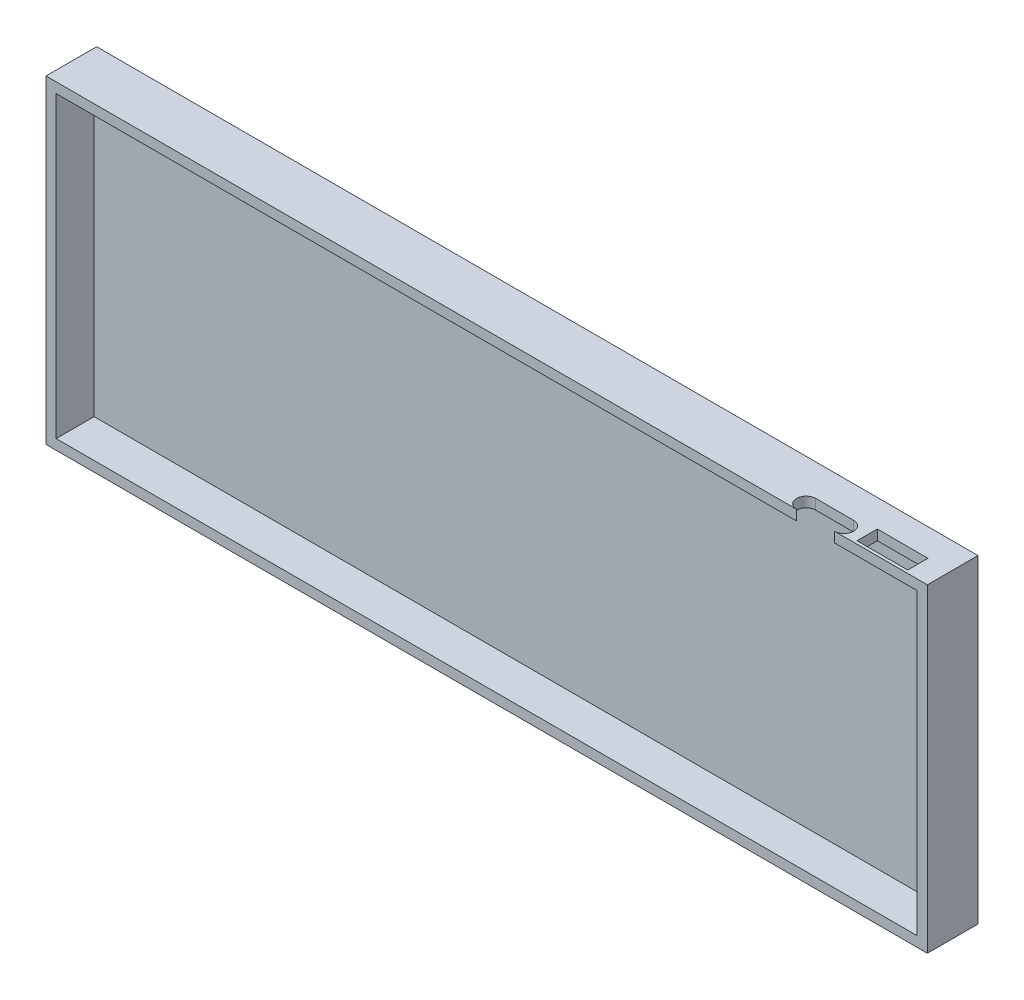
SolidWorks part; units mm, degrees
ref_plane "Front Plane" through (0, 0, 0) normal (0, 0, 1) x (1, 0, 0)
ref_plane "Top Plane" through (0, 0, 0) normal (0, 1, 0) x (1, 0, 0)
ref_plane "Right Plane" through (0, 0, 0) normal (1, 0, 0) x (0, 0, -1)
sketch "Sketch1" plane through (0, 0, 0) normal (0, 0, 1) x (1, 0, 0)
  line L1 (174, 63) -> (-174, 63)
  line L2 (174, 63) -> (174, -63)
  line L3 (174, -63) -> (-174, -63)
  line L4 (-174, 63) -> (-174, -63)
  line L5 (174, 63) -> (-174, -63) construction
  line L6 (174, -63) -> (-174, 63) construction
  point P0 (0, 0)
  dimension "D1" = 348
  dimension "D2" = 126
extrude "Boss-Extrude1" add sketch "Sketch1" along normal blind 20
sketch "Sketch2" plane through (0, 0, 20) normal (0, 0, 1) x (1, 0, 0)
  line L1 (170, 59) -> (-170, 59)
  line L2 (170, 59) -> (170, -59)
  line L3 (170, -59) -> (-170, -59)
  line L4 (-170, 59) -> (-170, -59)
  line L5 (170, 59) -> (-170, -59) construction
  line L6 (170, -59) -> (-170, 59) construction
  point P0 (0, 0)
  dimension "D1" = 340
  dimension "D2" = 118
extrude "Cut-Extrude1" cut sketch "Sketch2" against normal blind 15
sketch "Sketch4" plane through (0, 63, 0) normal (0, 1, 0) x (1, 0, 0)
  line L0 (122.39, -16.25) -> (137.39, -16.25) construction
  line L1 (122.39, -12.5) -> (137.39, -12.5)
  line L2 (122.39, -20) -> (137.39, -20)
  line L3 (174, -20) -> (174, 0) construction
  line L4 (174, -20) -> (-174, -20) construction
  arc A0 (122.39, -12.5) -> (122.39, -20) centre (122.39, -16.25) ccw
  arc A1 (137.39, -20) -> (137.39, -12.5) centre (137.39, -16.25) ccw
  point P2 (129.89, -16.25)
  dimension "D1" = 36.61
  dimension "D3" = 15
  dimension "D2" = 0
  dimension "D4" = 7.5
extrude "Cut-Extrude2" cut sketch "Sketch4" against normal up to next contours L2 A1 L1 A0
sketch "Sketch5" plane through (0, 63, 0) normal (0, 1, 0) x (1, 0, 0)
  line L0 (174, -20) -> (174, 0) construction
  line L1 (145.05, -10.81) -> (165.05, -10.81)
  line L2 (145.05, -10.81) -> (145.05, -18.81)
  line L3 (145.05, -18.81) -> (165.05, -18.81)
  line L4 (165.05, -10.81) -> (165.05, -18.81)
  line L5 (122.39, -18.81) -> (137.39, -18.81) construction
  line L6 (174, -20) -> (137.39, -20) construction
  dimension "D1" = 8.95
  dimension "D2" = 1.19
  dimension "D3" = 1.19
  dimension "D4" = 8
  dimension "D5" = 20
extrude "Cut-Extrude3" cut sketch "Sketch5" against normal up to next
